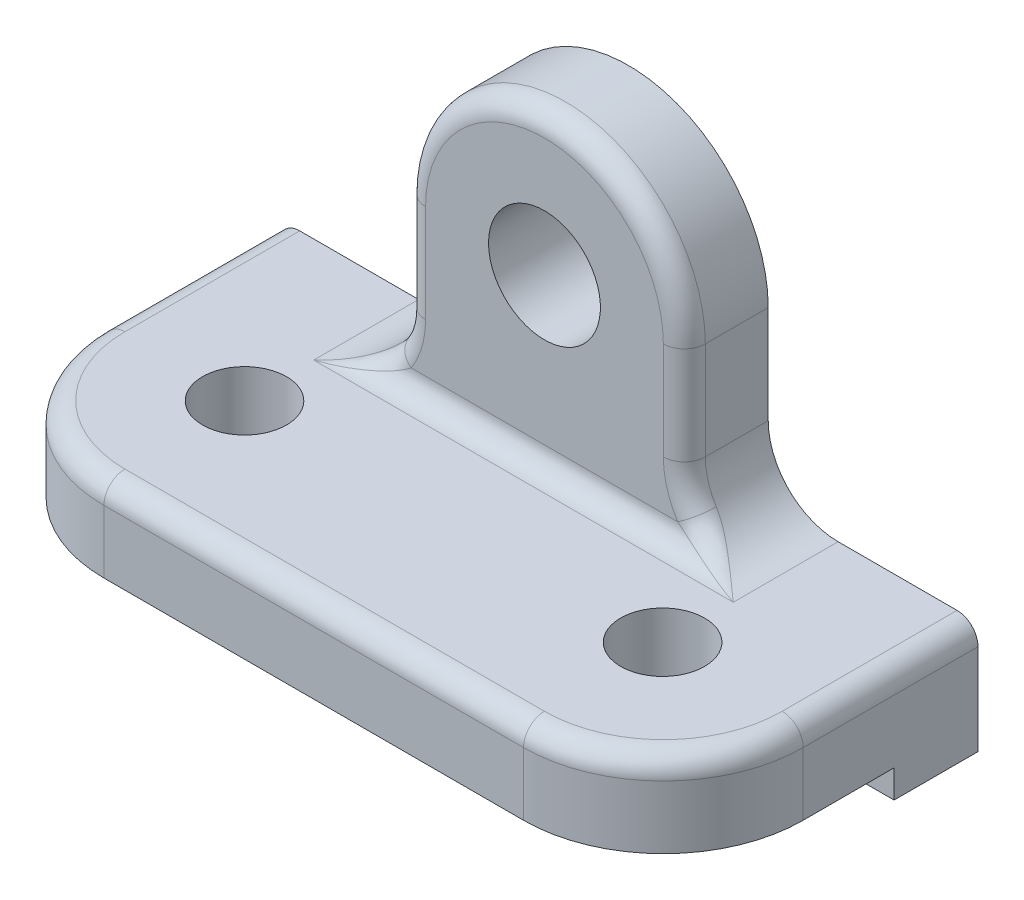
SolidWorks part; units mm, degrees
ref_plane "Ön Düzlem" through (0, 0, 0) normal (0, 0, 1) x (1, 0, 0)
ref_plane "Üst Düzlem" through (0, 0, 0) normal (0, 1, 0) x (1, 0, 0)
ref_plane "Sağ Düzlem" through (0, 0, 0) normal (1, 0, 0) x (0, 0, -1)
sketch "Çizim2" plane through (0, 0, 0) normal (0, 1, 0) x (1, 0, 0)
  line L0 (0, 28.6086) -> (0, -54.6719) construction
  line L1 (-30, -22.5) -> (30, -22.5)
  line L2 (-50, -2.5) -> (-50, 22.5)
  line L3 (-50, 22.5) -> (50, 22.5)
  line L4 (50, -2.5) -> (50, 22.5)
  line L5 (-50, -22.5) -> (50, 22.5) construction
  line L6 (-50, 22.5) -> (50, -22.5) construction
  arc A0 (30, -22.5) -> (50, -2.5) centre (30, -2.5) ccw
  arc A1 (-30, -22.5) -> (-50, -2.5) centre (-30, -2.5) cw
  circle A2 centre (-29.8957, -2.5) radius 6
  circle A3 centre (29.8957, -2.5) radius 6
  point P0 (0, 0)
  point P18 (0, 0)
  dimension "D3" = 20
  dimension "D1" = 45
  dimension "D2" = 100
  dimension "D6" = 25
extrude "Yükseklik-Ekstrüzyon1" add sketch "Çizim2" along normal blind 12
sketch "Çizim3" plane through (0, 0, 0) normal (0, -1, 0) x (1, 0, 0)
  line L0 (50, 2.5) -> (50, -22.5) construction
  line L1 (-50, -22.5) -> (50, -22.5)
  line L2 (-50, -22.5) -> (-50, -10.5)
  line L3 (-50, -10.5) -> (50, -10.5)
  line L4 (50, -22.5) -> (50, -10.5)
  dimension "D1" = 12
extrude "Yükseklik-Ekstrüzyon2" add sketch "Çizim3" along normal blind 4
fillet "Radyus1" radius 3 5 edges at (-50, 12, -10) (50, 12, -10) (44.1421, 12, 16.6421) (0, 12, 22.5) (-44.1421, 12, 16.6421)
sketch "Çizim4" plane through (0, 0, -22.5) normal (0, 0, -1) x (-1, 0, 0)
  line L0 (-47, 12) -> (47, 12) construction
  line L1 (-20, 36) -> (-20, 22)
  line L2 (-30, 12) -> (-47, 12)
  line L3 (0, 36) -> (0, -14.6022) construction
  line L4 (20, 36) -> (20, 22)
  line L5 (-30, 12) -> (30, 12)
  circle A0 centre (0, 36) radius 8
  arc A1 (20, 36) -> (-20, 36) centre (0, 36) ccw
  arc A2 (-20, 22) -> (-30, 12) centre (-30, 22) cw
  arc A3 (20, 22) -> (30, 12) centre (30, 22) ccw
  point P11 (-20, 12)
  dimension "D1" = 16
  dimension "D2" = 24
  dimension "D3" = 10
extrude "Yükseklik-Ekstrüzyon3" add sketch "Çizim4" against normal blind 12
fillet "Radyus2" radius 3 1 edges at (0, 12, -10.5)
fillet "Radyus3" radius 3 7 edges at (-24.3704, 13.7352, -10.2203) (-20.7422, 18.2194, -10.5) (-20, 29, -10.5) (24.3704, 13.7352, -10.2203) (20.7422, 18.2194, -10.5) (20, 29, -10.5) (0, 56, -10.5)
